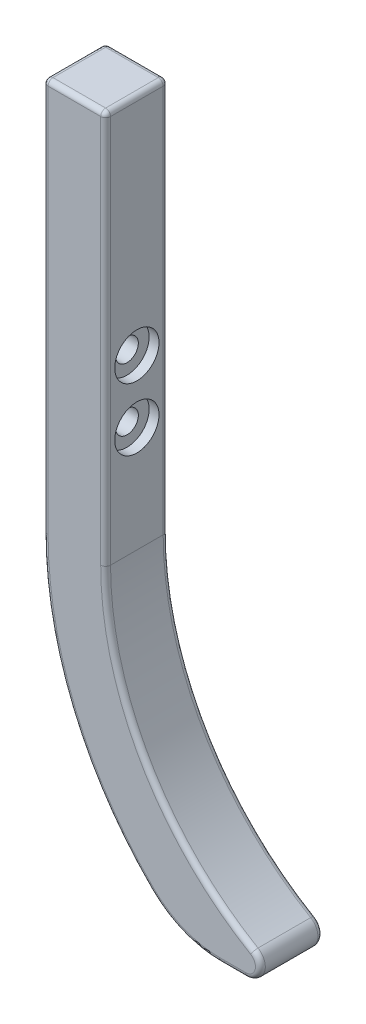
SolidWorks part; units mm, degrees
ref_plane "Front Plane" through (0, 0, 0) normal (0, 0, 1) x (1, 0, 0)
ref_plane "Top Plane" through (0, 0, 0) normal (0, 1, 0) x (1, 0, 0)
ref_plane "Right Plane" through (0, 0, 0) normal (1, 0, 0) x (0, 0, -1)
sketch "Sketch1" plane through (0, 0, 0) normal (0, 0, 1) x (1, 0, 0)
  line L1 (-60.8, 0) -> (-60.8, 80)
  line L2 (-60.8, 80) -> (-73.5, 80)
  line L3 (-73.5, 80) -> (-73.5, 0)
  line L4 (-18.2384, -58) -> (-45.147, -58)
  circle A0 centre (0, 0) radius 50.8 construction
  circle A1 centre (0, 0) radius 60.8 construction
  arc A2 (-18.2384, -58) -> (-60.8, 0) centre (0, 0) cw
  circle A4 centre (0, 60.8) radius 50.8 construction
  arc A5 (-73.5, 0) -> (-45.147, -58) centre (0, 0) ccw
  point P13 (0, 0)
  dimension "D1" = 101.6
  dimension "D2" = 121.6
  dimension "D5" = 101.6
  dimension "D3" = 12.7
  dimension "D4" = 80
  dimension "D6" = 138
extrude "Boss-Extrude1" add sketch "Sketch1" along normal blind 12.7
fillet "Fillet1" radius 3 1 edges at (-18.2384, -58, 6.35)
fillet "Fillet2" radius 20 1 edges at (-45.147, -58, 6.35)
sketch "Sketch2" plane through (-60.8, 0, 0) normal (1, 0, 0) x (0, 0, -1)
  line L0 (-12.7, 80) -> (0, 80) construction
  line L1 (-12.7, 0) -> (-12.7, 80) construction
  circle A0 centre (-6.35, 21.58) radius 2.3
  circle A1 centre (-6.35, 34.28) radius 2.3
  circle A2 centre (-6.35, 34.28) radius 4.5
  circle A3 centre (-6.35, 21.58) radius 4.5
  dimension "D4" = 4.6
  dimension "D5" = 9
  dimension "D6" = 9
  dimension "D1" = 58.42
  dimension "D2" = 12.7
  dimension "D3" = 6.35
extrude "Cut-Extrude1" cut sketch "Sketch2" against normal up to next contours A1 | A0 region at (-60.8, 21.58, 6.35) region at (-60.8, 34.28, 6.35)
extrude "Cut-Extrude2" cut sketch "Sketch2<3>" against normal blind 2 contours A2 A1 | A3 A0 region at (-60.8, 34.28, 10.7227) region at (-60.8, 21.58, 10.7227)
sketch "Sketch2<3>" plane through (-60.8, 0, 0) normal (1, 0, 0) x (0, 0, -1) same geometry as "Sketch2"
fillet "Fillet3" radius 1 14 edges at (-73.5, 40, 0) (-67.8417, -28.2799, 0) (-45.2718, -56.4948, 0) (-34.9965, -58, 0) (-29.4386, -55.7878, 0) (-52.7734, -30.1928, 0) (-73.5, 40, 12.7) (-67.8417, -28.2799, 12.7) (-45.2718, -56.4948, 12.7) (-34.9965, -58, 12.7) (-29.4386, -55.7878, 12.7) (-52.7734, -30.1928, 12.7) (-60.8, 40, 0) (-60.8, 40, 12.7)
fillet "Fillet4" radius 1 8 edges at (-61.0929, 80, 12.4071) (-60.8, 80, 6.35) (-61.0929, 80, 0.2929) (-67.15, 80, 0) (-73.2071, 80, 0.2929) (-73.5, 80, 6.35) (-73.2071, 80, 12.4071) (-67.15, 80, 12.7)
